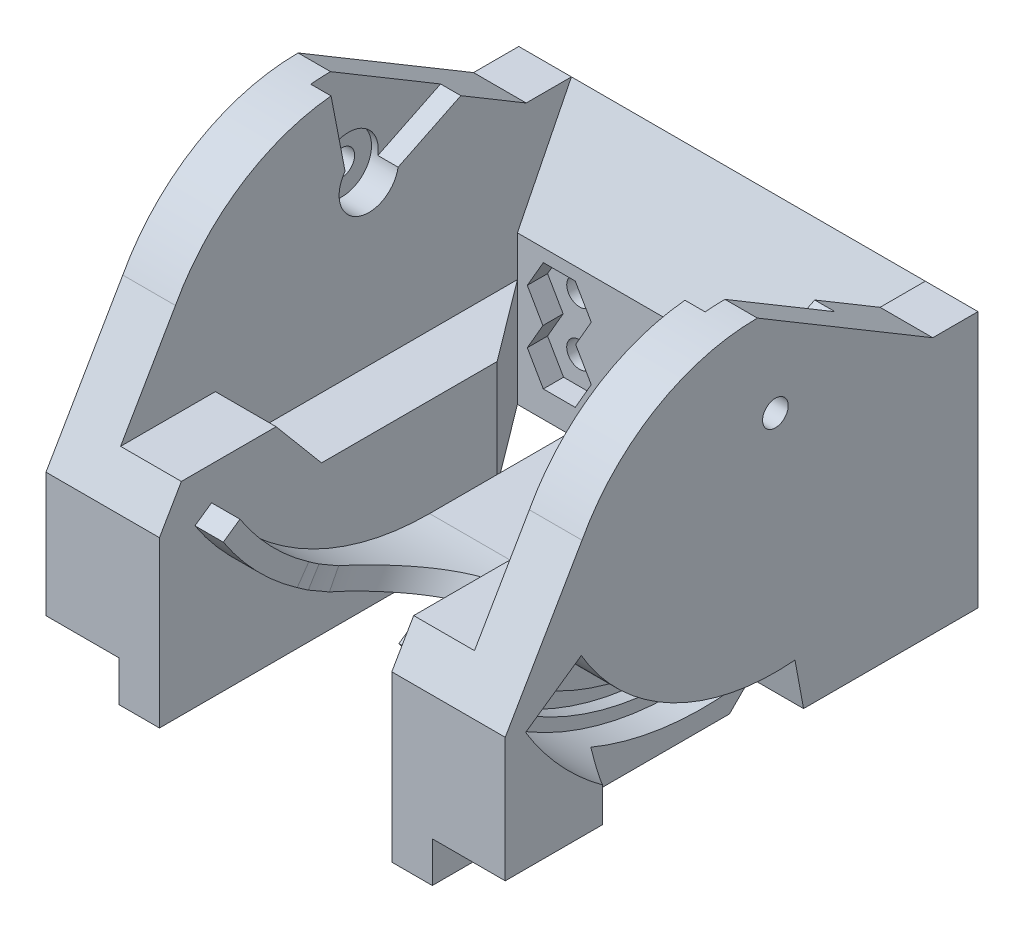
SolidWorks part; units mm, degrees
ref_plane "Alzado" through (0, 0, 0) normal (0, 0, 1) x (1, 0, 0)
ref_plane "Planta" through (0, 0, 0) normal (0, 1, 0) x (1, 0, 0)
ref_plane "Vista lateral" through (0, 0, 0) normal (1, 0, 0) x (0, 0, -1)
sketch "Croquis1" plane through (0, 0, 0) normal (0, 0, 1) x (1, 0, 0)
  line L1 (-48.8873, 14.6225) -> (-14.8873, 14.6225)
  line L2 (-48.8873, 14.6225) -> (-48.8873, -4.3775)
  line L3 (-48.8873, -4.3775) -> (-14.8873, -4.3775)
  line L4 (-14.8873, 14.6225) -> (-14.8873, -4.3775)
  dimension "D1" = 19
  dimension "D2" = 34
extrude "Saliente-Extruir1" add sketch "Croquis1" along normal blind 35
sketch "Croquis2" plane through (0, -4.3775, 0) normal (0, -1, 0) x (1, 0, 0)
  line L0 (-48.8873, 35) -> (-14.8873, 35) construction
  line L1 (-44.9873, 35) -> (-18.7873, 35)
  line L2 (-44.9873, 35) -> (-44.9873, 4)
  line L3 (-44.9873, 4) -> (-18.7873, 4)
  line L4 (-18.7873, 35) -> (-18.7873, 4)
  line L5 (-48.8873, 35) -> (-48.8873, 0) construction
  line L6 (-14.8873, 35) -> (-14.8873, 0) construction
  line L7 (-48.8873, 0) -> (-14.8873, 0) construction
  dimension "D1" = 3.9
  dimension "D2" = 3.9
  dimension "D3" = 26.2
  dimension "D4" = 4
extrude "Cortar-Extruir1" cut sketch "Croquis2" against normal blind 25
sketch "Croquis4" plane through (-18.7873, 0, 0) normal (-1, 0, 0) x (0, 0, 1)
  line L0 (4, 14.6225) -> (4, 6.6225)
  line L1 (4, 14.6225) -> (4, -4.3775) construction
  line L2 (4, 6.6225) -> (0, 14.6225)
  line L3 (0, 14.6225) -> (4, 14.6225)
extrude "Cortar-Extruir3" cut sketch "Croquis4" along normal up to vertex (26.2 mm away) up to point (-44.9873, 14.6225, 4)
sketch "Croquis9" plane through (-14.8873, 0, 0) normal (1, 0, 0) x (0, 0, -1)
  line L0 (-35, 14.6225) -> (0, 14.6225) construction
  line L1 (-29.3158, 14.6225) -> (-3.3495, 14.6225)
  line L7 (-35, -4.3775) -> (0, -4.3775) construction
  arc A0 (-29.3158, 14.6225) -> (-3.3495, 14.6225) centre (-16.3327, 7.6225) cw
  dimension "D2" = 12
extrude "Saliente-Extruir2" add sketch "Croquis9" against normal up to vertex (34 mm away) up to point (-48.8873, 14.6225, 35)
sketch "Croquis10" plane through (0, 14.6225, 0) normal (0, -1, 0) x (1, 0, 0)
  line L1 (-44.9873, 29.3158) -> (-18.7873, 29.3158)
  line L2 (-44.9873, 29.3158) -> (-44.9873, 3.3495)
  line L3 (-44.9873, 3.3495) -> (-18.7873, 3.3495)
  line L4 (-18.7873, 29.3158) -> (-18.7873, 3.3495)
extrude "Cortar-Extruir4" cut sketch "Croquis10" against normal blind 10
sketch "Croquis18" plane through (0, 0, 0) normal (0, 0, -1) x (-1, 0, 0)
  line L0 (48.8873, -4.3775) -> (14.8873, -4.3775) construction
  line L2 (48.8873, 14.6225) -> (48.8873, -4.3775) construction
  circle A0 centre (41.8873, -0.3775) radius 0.95
  circle A1 centre (21.8873, -0.3775) radius 0.95
  circle A2 centre (21.8873, 3.6225) radius 0.95
  circle A3 centre (41.8873, 3.6225) radius 0.95
  dimension "D1" = 4
  dimension "D2" = 7
  dimension "D5" = 4
  dimension "D3" = 2
  dimension "D4" = 2
extrude "Cortar-Extruir11" cut sketch "Croquis18" against normal up to vertex (4 mm away) up to point (-18.7873, -4.3775, 4)
sketch "Croquis19" plane through (0, 0, 4) normal (0, 0, 1) x (1, 0, 0)
  line L0 (-39.5201, -0.3775) -> (-40.6748, 1.6225)
  line L1 (-19.5201, -0.3775) -> (-20.6748, 1.6225)
  line L3 (-23.0997, 1.6225) -> (-24.2544, -0.3775)
  line L4 (-24.2544, -0.3775) -> (-23.0708, -2.4275)
  line L5 (-23.0708, -2.4275) -> (-20.7037, -2.4275)
  line L6 (-20.7037, -2.4275) -> (-19.5201, -0.3775)
  line L8 (-43.0997, 1.6225) -> (-44.2544, -0.3775)
  line L9 (-44.2544, -0.3775) -> (-43.0708, -2.4275)
  line L10 (-43.0708, -2.4275) -> (-40.7037, -2.4275)
  line L11 (-40.7037, -2.4275) -> (-39.5201, -0.3775)
  line L12 (-39.5201, 3.6225) -> (-40.7037, 5.6725)
  line L13 (-40.7037, 5.6725) -> (-43.0708, 5.6725)
  line L14 (-43.0708, 5.6725) -> (-44.2544, 3.6225)
  line L15 (-44.2544, 3.6225) -> (-43.0997, 1.6225)
  line L17 (-40.6748, 1.6225) -> (-39.5201, 3.6225)
  line L18 (-19.5201, 3.6225) -> (-20.7037, 5.6725)
  line L19 (-20.7037, 5.6725) -> (-23.0708, 5.6725)
  line L20 (-23.0708, 5.6725) -> (-24.2544, 3.6225)
  line L21 (-24.2544, 3.6225) -> (-23.0997, 1.6225)
  line L23 (-20.6748, 1.6225) -> (-19.5201, 3.6225)
  line L29 (-43.0708, 1.5725) -> (-40.7037, 1.5725) [skipped]
  line L30 (-23.0708, 1.5725) -> (-20.7037, 1.5725) [skipped]
  line L31 (-20.7037, 1.6725) -> (-23.0708, 1.6725) [skipped]
  circle A0 centre (-21.8873, -0.3775) radius 2.05 construction
  circle A1 centre (-41.8873, -0.3775) radius 2.05 construction
  circle A2 centre (-41.8873, 3.6225) radius 2.05 construction
  circle A3 centre (-21.8873, 3.6225) radius 2.05 construction
  dimension "D1" = 4.1
  dimension "D2" = 2
  dimension "D3" = 2
extrude "Cortar-Extruir12" cut sketch "Croquis19" against normal blind 1.5
sketch "Croquis21" plane through (-14.8873, 0, 0) normal (1, 0, 0) x (0, 0, -1)
  line L0 (0, -4.3775) -> (0, 14.6225) construction
  line L2 (-35, -4.3775) -> (0, -4.3775) construction
  circle A0 centre (-15, 15.6225) radius 0.95
  dimension "D1" = 15
  dimension "D2" = 20
extrude "Cortar-Extruir14" cut sketch "Croquis21" against normal up to vertex (34 mm away) up to point (-48.8873, 14.6225, 3.3495)
sketch "Croquis23" plane through (0, -4.3775, 0) normal (0, -1, 0) x (1, 0, 0)
  line L0 (-44.9873, 35) -> (-40.4873, 35)
  line L1 (-40.4873, 35) -> (-40.4873, 10)
  line L2 (-40.4873, 10) -> (-44.9873, 4)
  line L3 (-44.9873, 35) -> (-44.9873, 4) construction
  line L4 (-44.9873, 4) -> (-44.9873, 35)
  line L5 (-18.7873, 35) -> (-23.2873, 35)
  line L6 (-23.2873, 35) -> (-23.2873, 10)
  line L7 (-23.2873, 10) -> (-18.7873, 4)
  line L8 (-18.7873, 4) -> (-18.7873, 35)
  dimension "D1" = 25
  dimension "D2" = 25
extrude "Saliente-Extruir3" add sketch "Croquis23" against normal blind 8
sketch "Croquis25" plane through (0, -4.3775, 0) normal (0, -1, 0) x (1, 0, 0)
  line L0 (-40.4873, 35) -> (-43.4873, 35)
  line L1 (-20.2873, 35) -> (-23.2873, 35)
  line L2 (-43.4873, 35) -> (-43.4873, 10)
  line L3 (-43.4873, 10) -> (-40.4873, 10)
  line L4 (-40.4873, 35) -> (-40.4873, 10)
  line L10 (-20.2873, 35) -> (-20.2873, 10)
  line L11 (-20.2873, 10) -> (-23.2873, 10)
  line L12 (-23.2873, 35) -> (-23.2873, 10)
  dimension "D1" = 3
  dimension "D2" = 3
extrude "Saliente-Extruir4" add sketch "Croquis25" along normal blind 3
sketch "Croquis43" plane through (0, 3.6225, 0) normal (0, 1, 0) x (1, 0, 0)
  line L0 (-23.2873, -35) -> (-23.2873, -10) construction
  line L1 (-18.7873, -35) -> (-23.2873, -35)
  line L2 (-18.7873, -35) -> (-18.7873, -23)
  line L3 (-18.7873, -23) -> (-23.2873, -23)
  line L4 (-23.2873, -35) -> (-23.2873, -23)
  line L5 (-44.9873, -35) -> (-44.9873, -4) construction
  line L6 (-40.4873, -35) -> (-44.9873, -35)
  line L7 (-40.4873, -35) -> (-40.4873, -23)
  line L8 (-40.4873, -23) -> (-44.9873, -23)
  line L9 (-44.9873, -35) -> (-44.9873, -23)
  dimension "D1" = 12
  dimension "D2" = 12
extrude "Saliente-Extruir8" add sketch "Croquis43" along normal blind 4
sketch "Croquis27" plane through (-14.8873, 0, 0) normal (1, 0, 0) x (0, 0, -1)
  line L0 (-13.5494, -0.9426) -> (-12.6355, -5.8873)
  line L1 (-33.492, 4.3837) -> (-29.3712, 7.2574)
  arc A2 (-29.3712, 7.2574) -> (-13.5494, -0.9426) centre (-15, 15.6225) ccw
  arc A3 (-33.492, 4.3837) -> (-12.6355, -5.8873) centre (-15, 15.6225) ccw
  dimension "D2" = 21.6395
extrude "Cortar-Extruir18" cut sketch "Croquis27" against normal blind 7.4
sketch "Croquis24" plane through (-14.8873, 0, 0) normal (1, 0, 0) x (0, 0, -1)
  line L0 (-15, -3.6275) -> (-15, -5.1273)
  line L1 (-31.1427, 5.1356) -> (-32.3723, 4.2754)
  arc A2 (-31.1427, 5.1356) -> (-15, -3.6275) centre (-15, 15.6225) ccw
  arc A3 (-32.3723, 4.2754) -> (-15, -5.1273) centre (-15, 15.6225) ccw
  dimension "D1" = 19.25
  dimension "D2" = 20.7498
extrude "Cortar-Extruir16" cut sketch "Croquis24" against normal up to vertex (34 mm away) up to point (-48.8873, -4.3775, 35)
sketch "Croquis29" plane through (-18.7873, 0, 0) normal (-1, 0, 0) x (0, 0, 1)
  line L0 (17.7974, 22.2996) -> (16.5, 15.6225)
  line L1 (6.2969, 18.4321) -> (13.7431, 14.804)
  arc A0 (6.2969, 18.4321) -> (17.7974, 22.2996) centre (16.3327, 7.6225) cw
  arc A1 (29.3158, 14.6225) -> (3.3495, 14.6225) centre (16.3327, 7.6225) ccw construction
  arc A2 (16.5, 15.6225) -> (13.7431, 14.804) centre (15, 15.6225) cw
extrude "Cortar-Extruir20" cut sketch "Croquis29" against normal blind 1.5
extrude "Cortar-Extruir21" cut sketch "Croquis29<2>" along normal blind 27.7
sketch "Croquis29<2>" plane through (-18.7873, 0, 0) normal (-1, 0, 0) x (0, 0, 1) same geometry as "Croquis29"
sketch "Croquis30" plane through (-48.8873, 0, 0) normal (-1, 0, 0) x (0, 0, 1)
  line L0 (29.3158, 14.6225) -> (35, 4.8278)
  line L1 (35, 14.6225) -> (35, -4.3775) construction
  line L2 (35, 4.8278) -> (35, 14.6225)
  line L3 (35, 14.6225) -> (29.3158, 14.6225)
extrude "Cortar-Extruir22" cut sketch "Croquis30" against normal up to vertex (34 mm away) up to point (-14.8873, 14.6225, 35)
sketch "Croquis35" plane through (0, -4.3775, 0) normal (0, -1, 0) x (1, 0, 0)
  line L0 (-20.2873, 23.2623) -> (-14.8873, 23.2623)
  line L2 (-20.2873, 23.2623) -> (-14.8873, 23.2623) construction
  line L4 (-14.8873, 23.2623) -> (-14.8873, 27.7963)
  line L5 (-14.8873, 35) -> (-14.8873, 23.2623) construction
  line L6 (-14.8873, 27.7963) -> (-20.2873, 23.2623)
extrude "Cortar-Extruir23" cut sketch "Croquis35" against normal blind 3
sketch "Croquis36" plane through (-18.7873, 0, 0) normal (-1, 0, 0) x (0, 0, 1)
  circle A0 centre (15, 15.6225) radius 2.2
extrude "Cortar-Extruir24" cut sketch "Croquis36" against normal blind 2
extrude "Cortar-Extruir25" cut sketch "Croquis36<2>" along normal blind 28.2
sketch "Croquis36<2>" plane through (-18.7873, 0, 0) normal (-1, 0, 0) x (0, 0, 1) same geometry as "Croquis36"
sketch "Croquis38" plane through (-48.8873, 0, 0) normal (-1, 0, 0) x (0, 0, 1)
  line L0 (3.3495, 14.6225) -> (16.3327, 22.3725)
  line L1 (16.3327, 22.3725) -> (3.3495, 22.3725)
  line L2 (3.3495, 22.3725) -> (3.3495, 14.6225)
  arc A0 (29.3158, 14.6225) -> (3.3495, 14.6225) centre (16.3327, 7.6225) ccw construction
extrude "Cortar-Extruir26" cut sketch "Croquis38" against normal up to vertex (34 mm away) up to point (-14.8873, 14.6225, 3.3495)
sketch "Croquis40" plane through (-48.8873, 0, 0) normal (-1, 0, 0) x (0, 0, 1)
  line L0 (24.4625, 4.9679) -> (27.805, 0.9845)
  line L1 (27.805, 0.9845) -> (27.1921, 0.4702)
  line L2 (27.1921, 0.4702) -> (23.8496, 4.4537)
  line L3 (23.5, 4.1807) -> (26.4826, -0.0789)
  line L4 (26.4826, -0.0789) -> (25.8272, -0.5377)
  line L5 (25.8272, -0.5377) -> (22.8446, 3.7219)
  line L6 (22.4696, 3.4848) -> (25.0696, -1.0186)
  line L7 (24.4625, 4.9679) -> (23.8496, 4.4537)
  line L8 (25.0696, -1.0186) -> (24.3768, -1.4186)
  line L9 (24.3768, -1.4186) -> (21.7768, 3.0848)
  line L10 (22.8446, 3.7219) -> (23.5, 4.1807)
  line L11 (21.3819, 2.8831) -> (23.5795, -1.8297)
  line L12 (23.5795, -1.8297) -> (22.8544, -2.1678)
  line L13 (22.4696, 3.4848) -> (21.7768, 3.0848)
  line L14 (22.8544, -2.1678) -> (20.6568, 2.545)
  line L16 (21.3819, 2.8831) -> (20.6568, 2.545)
  circle A1 centre (15, 15.6225) radius 0.95 construction
  dimension "D2" = 14.2443
  dimension "D3" = 14.248
  dimension "D4" = 14.2464
  dimension "D5" = 0.8
  dimension "D6" = 14.2429
  dimension "D8" = 0.8
  dimension "D9" = 0.8
  dimension "D11" = 0.8
extrude "Cortar-Extruir27" cut sketch "Croquis40" against normal blind 1
sketch "Croquis41" plane through (-20.2873, 0, 0) normal (1, 0, 0) x (0, 0, -1)
  line L0 (-10, -4.3775) -> (-10, -7.3775)
  line L1 (-10, -7.3775) -> (-10, -4.3775) construction
  line L2 (-10, -7.3775) -> (-13, -7.3775)
  line L3 (-10, -7.3775) -> (-35, -7.3775) construction
  line L4 (-13, -7.3775) -> (-10, -4.3775)
extrude "Cortar-Extruir28" cut sketch "Croquis41" against normal up to vertex (23.2 mm away) up to point (-43.4873, -7.3775, 10)
sketch "Croquis44" plane through (-18.7873, 0, 0) normal (-1, 0, 0) x (0, 0, 1)
  line L0 (23, 7.6225) -> (26.3626, 7.6225)
  line L1 (33.3781, 7.6225) -> (23, 7.6225) construction
  line L2 (26.3626, 7.6225) -> (23, 3.6225)
  line L3 (23, 3.6225) -> (23, 7.6225)
extrude "Cortar-Extruir29" cut sketch "Croquis44" along normal up to vertex (26.2 mm away) up to point (-44.9873, 7.6225, 23)
sketch "Croquis45" plane through (-23.2873, 0, 0) normal (-1, 0, 0) x (0, 0, 1)
  line L0 (31.1427, 5.1356) -> (32.3723, 4.2754)
  line L1 (15, -3.6275) -> (15, -5.1273)
  line L2 (15, -3.6275) -> (15, -5.1273) construction
  arc A0 (15, -3.6275) -> (31.1427, 5.1356) centre (15, 15.6225) ccw construction
  arc A1 (32.3723, 4.2754) -> (15, -5.1273) centre (15, 15.6225) cw
  arc A2 (15, -3.6275) -> (31.1427, 5.1356) centre (15, 15.6225) ccw
extrude "Saliente-Extruir9" add sketch "Croquis45" along normal up to vertex (17.2 mm away) separate body up to point (-40.4873, -7.3775, 13)
ref_plane "Plano1" through (-31.8873, 4.2754, 32.3723) normal (1, 0, 0) x (0, 0, -1)
sketch "Croquis47" plane through (-31.8873, 4.2754, 32.3723) normal (1, 0, 0) x (0, 0, -1)
  line L0 (17.3723, 11.3471) -> (17.3723, -21.3789) construction
  line L1 (17.3723, 11.3471) -> (0.4676, -24.9052) construction
  line L2 (17.3723, 11.3471) -> (-2.6277, -23.2939) construction
  line L3 (17.3723, 11.3471) -> (-5.5707, -21.419) construction
  line L4 (17.3723, 11.3471) -> (-5.5707, -21.419)
  line L5 (17.3723, 11.3471) -> (-2.6277, -23.2939)
  line L6 (17.3723, 11.3471) -> (0.4676, -24.9052)
  dimension "D1" = 25
  dimension "D2" = 30
  dimension "D3" = 35
ref_plane "Plano2" through (-31.8873, -17.1435, 37.9431) normal (0, -0.8192, 0.5736) x (-1, 0, 0)
sketch "Croquis48" plane through (-31.8873, -17.1435, 37.9431) normal (0, -0.8192, 0.5736) x (-1, 0, 0)
  line L3 (6.5, 0) -> (6.5, -15)
  line L4 (6.5, -15) -> (-6.5, -15)
  line L5 (-6.5, -15) -> (-6.5, 0)
  arc A2 (6.5, 0) -> (-6.5, 0) centre (0, 0) ccw
ref_plane "Plano3" through (-31.8873, -19.0185, 35) normal (0, -0.866, 0.5) x (-1, 0, 0)
ref_plane "Plano4" through (-31.8873, -20.6298, 31.9047) normal (0, -0.9063, 0.4226) x (-1, 0, 0)
sketch "Croquis49" plane through (-31.8873, -19.0185, 35) normal (0, -0.866, 0.5) x (-1, 0, 0)
  circle A0 centre (0, 0) radius 6.5
sketch "Croquis50" plane through (-31.8873, -20.6298, 31.9047) normal (0, -0.9063, 0.4226) x (-1, 0, 0)
  circle A0 centre (0, 0) radius 6.5
sweep "Cortar-Barrer2" cut profiles "Croquis48" path "Croquis47"
sketch "Croquis51" plane through (-31.8873, 4.2754, 32.3723) normal (1, 0, 0) x (0, 0, -1)
  line L0 (17.3723, 11.3471) -> (-2.6277, -23.2939)
sweep "Cortar-Barrer3" cut profiles "Croquis49" path "Croquis51"
sketch "Croquis52" plane through (-31.8873, 4.2754, 32.3723) normal (1, 0, 0) x (0, 0, -1)
  line L0 (17.3723, 11.3471) -> (0.4676, -24.9052)
sweep "Cortar-Barrer4" cut profiles "Croquis50" path "Croquis52"
sketch "Croquis53" plane through (0, 0, 15) normal (0, 0, -1) x (-1, 0, 0)
  line L1 (40.4873, -5.1273) -> (23.2873, -5.1273)
  line L2 (40.4873, -5.1273) -> (40.4873, -3.6275)
  line L3 (40.4873, -3.6275) -> (23.2873, -3.6275)
  line L4 (23.2873, -5.1273) -> (23.2873, -3.6275)
extrude "Saliente-Extruir13" add sketch "Croquis53" along normal up to vertex (11 mm away) separate body up to point (-18.7873, -4.3775, 4)
sketch "Croquis55" plane through (-40.4873, 0, 0) normal (-1, 0, 0) x (0, 0, 1)
  line L0 (4, -5.1273) -> (4, -4.3774)
  line L1 (4, -5.1273) -> (4, -3.6275) construction
  line L2 (4, -4.3774) -> (0, -4.3774)
  line L3 (0, -4.3774) -> (4, -5.1273)
extrude "Saliente-Extruir14" add sketch "Croquis55" against normal up to vertex (17.2 mm away) up to point (-23.2873, -5.1273, 4)
